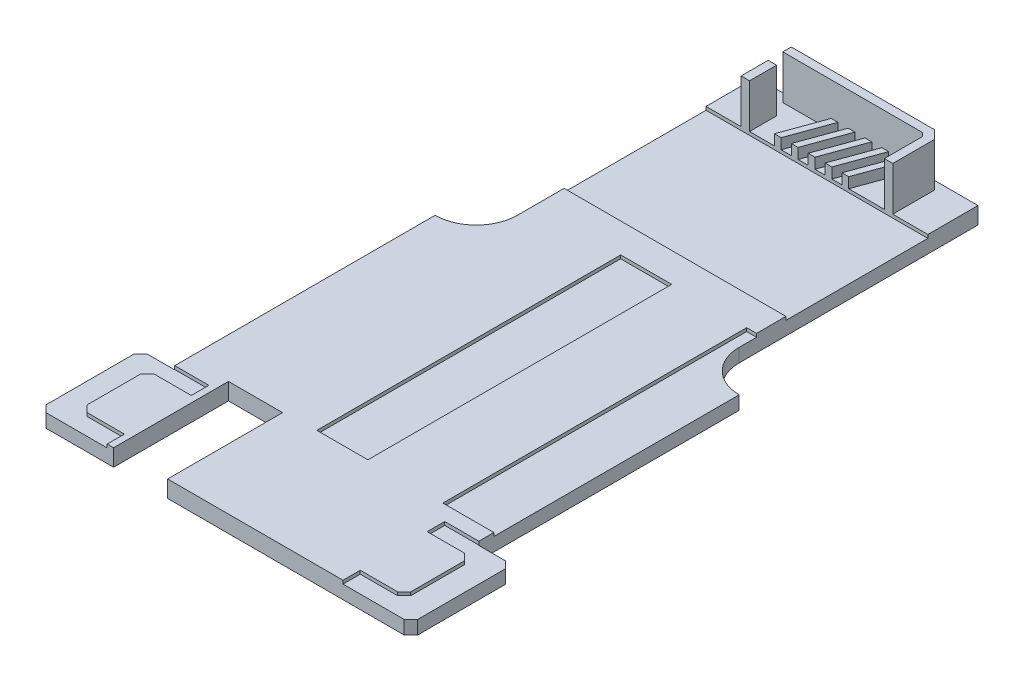
SolidWorks part; units mm, degrees
ref_plane "Front Plane" through (0, 0, 0) normal (0, 0, 1) x (1, 0, 0)
ref_plane "Top Plane" through (0, 0, 0) normal (0, 1, 0) x (1, 0, 0)
ref_plane "Right Plane" through (0, 0, 0) normal (1, 0, 0) x (0, 0, -1)
sketch "Sketch1" plane through (0, 0, 0) normal (0, 1, 0) x (1, 0, 0)
  line L1 (-45, 95) -> (45, 95)
  line L2 (-45, 95) -> (-45, -95)
  line L3 (-45, -95) -> (45, -95)
  line L4 (45, 95) -> (45, -95)
  line L5 (-45, 95) -> (45, -95) construction
  line L6 (-45, -95) -> (45, 95) construction
  point P0 (0, 0)
  dimension "D1" = 190
  dimension "D2" = 90
extrude "Boss-Extrude1" add sketch "Sketch1" along normal blind 5 contours L2 L1 L4 L3
sketch "Sketch2" plane through (0, 0, 0) normal (0, 1, 0) x (1, 0, 0)
  line L0 (-45, 95) -> (-45, -95) construction
  line L1 (-45, -65) -> (-55, -65)
  line L2 (-45, -65) -> (-45, -95)
  line L3 (-45, -95) -> (-55, -95)
  line L4 (-55, -65) -> (-55, -95)
  line L5 (45, 95) -> (45, -95) construction
  line L6 (45, -65) -> (55, -65)
  line L7 (45, -65) -> (45, -95)
  line L8 (45, -95) -> (55, -95)
  line L9 (55, -65) -> (55, -95)
  line L10 (-45, -95) -> (45, -95) construction
  dimension "D1" = 30
  dimension "D2" = 10
extrude "Boss-Extrude2" add sketch "Sketch2" along normal blind 5
chamfer "Chamfer1" distance 2 angle 45 4 edges at (55, 2.5, 95) (55, 2.5, 65) (-55, 2.5, 95) (-55, 2.5, 65)
sketch "Sketch3" plane through (0, 5, 0) normal (0, 1, 0) x (1, 0, 0)
  line L0 (-53, -95) -> (53, -95) construction
  line L1 (-33, -95) -> (-17, -95)
  line L2 (-33, -95) -> (-33, -61)
  line L3 (-33, -61) -> (-17, -61)
  line L4 (-17, -95) -> (-17, -61)
  line L5 (-55, -67) -> (-55, -93) construction
  dimension "D1" = 22
  dimension "D2" = 16
  dimension "D3" = 34
extrude "Cut-Extrude1" cut sketch "Sketch3" against normal blind 50 contours L2 L1 L4 L3
sketch "Sketch4" plane through (0, 5, 0) normal (0, 1, 0) x (1, 0, 0)
  line L0 (-45, 80.1598) -> (-45, 38.1598)
  line L1 (-45, 95) -> (-45, -65) construction
  line L2 (-48, 80.1598) -> (48, 80.1598) construction
  line L4 (-45, 38.1598) -> (45, 38.1598)
  line L5 (45, 95) -> (45, -65) construction
  line L6 (45, 38.1598) -> (45, 80.1598)
  line L7 (45, 80.1598) -> (-45, 80.1598)
  dimension "D1" = 42
extrude "Cut-Extrude2" cut sketch "Sketch4" against normal blind 1
sketch "Sketch7" plane through (0, 5, 0) normal (0, 1, 0) x (1, 0, 0)
  line L0 (-7.3823, 29.4629) -> (-7.3823, -60.4534)
  line L1 (-7.3823, -60.4534) -> (7.7177, -60.4534)
  line L2 (7.7177, -60.4534) -> (7.7177, 29.4629)
  line L3 (7.7177, 29.4629) -> (-7.3823, 29.4629)
  line L4 (29.9, 29.4629) -> (29.9, -60.4534)
  line L5 (29.9, -60.4534) -> (45, -60.4534)
  line L6 (45, 38.1598) -> (45, -65) construction
  line L7 (45, -60.4534) -> (45, 29.4629)
  line L8 (45, 29.4629) -> (29.9, 29.4629)
  line M17 (45, -65) -> (45, 38.1598)
  dimension "D1" = 15.1
  dimension "D2" = 15.1
extrude "Cut-Extrude7" cut sketch "Sketch7" against normal blind 1 contours L8 L4 L5 M17 | L3 L0 L1 L2 region at (37.45, 5, 15.4953)
sketch "Sketch8" plane through (0, 5, 0) normal (0, 1, 0) x (1, 0, 0)
  line L1 (-35, -65) -> (-35, -70) construction
  line L2 (-35, -70) -> (-46, -70) construction
  line L3 (-46, -70) -> (-48, -72) construction
  line L4 (-48, -72) -> (-48, -88) construction
  line L5 (-48, -88) -> (-46, -90) construction
  line L6 (-46, -90) -> (-35, -90) construction
  line L7 (-35, -90) -> (-35, -95) construction
  line L8 (-53, -95) -> (-33, -95) construction
  line L9 (-35, -95) -> (-35, -90) construction
  line L10 (-35, -95) -> (-53, -95) construction
  line L11 (-53, -95) -> (-55, -93) construction
  line L12 (-55, -93) -> (-55, -67) construction
  line L13 (-55, -67) -> (-53, -65) construction
  line L14 (-53, -65) -> (-35, -65) construction
  line L15 (-34.9, -70.1) -> (-45.9586, -70.1)
  line L16 (-45.9586, -70.1) -> (-47.9, -72.0414)
  line L17 (-47.9, -72.0414) -> (-47.9, -87.9586)
  line L18 (-47.9, -87.9586) -> (-45.9586, -89.9)
  line L19 (-45.9586, -89.9) -> (-34.9, -89.9)
  line L20 (-34.9, -89.9) -> (-34.9, -95.1)
  line L21 (-34.9, -95.1) -> (-53.0414, -95.1)
  line L22 (-53.0414, -95.1) -> (-55.1, -93.0414)
  line L23 (-55.1, -93.0414) -> (-55.1, -66.9586)
  line L24 (-55.1, -66.9586) -> (-53.0414, -64.9)
  line L25 (-53.0414, -64.9) -> (-34.9, -64.9)
  line L26 (-34.9, -64.9) -> (-34.9, -70.1)
  dimension "D1" = 0.1
extrude "Cut-Extrude8" cut sketch "Sketch8" against normal blind 1
mirror "Mirror1" about plane through (0, 0, 0) normal (1, 0, 0) of "Cut-Extrude8"
sketch "Sketch14" plane through (0, 0, 0) normal (0, 1, 0) x (1, 0, 0)
  line L0 (-45, 47.2671) -> (-34.685, 30.799)
  line L1 (-45, 80.1598) -> (-45, 38.1598) construction
  line L2 (-45, 38.1598) -> (-45, -64.9) construction
  line L3 (-45, 47.2671) -> (-45, 12.1668)
  line L4 (0, -6.2305) -> (0, 15.6399) construction
  line L5 (45, 47.2671) -> (45, 12.1668)
  line L6 (45, 47.2671) -> (34.685, 30.799)
  arc A0 (-34.685, 30.799) -> (-45, 12.1668) centre (-45, 24.3381) cw
  arc A1 (34.685, 30.799) -> (45, 12.1668) centre (45, 24.3381) ccw
extrude "Cut-Extrude9" cut sketch "Sketch14" along normal through all both and the other way through all
sketch "Sketch15" plane through (0, 0, 0) normal (0, 1, 0) x (1, 0, 0)
  line L0 (-34.685, 30.799) -> (-39.2956, 38.1598) construction
  line L2 (-34.685, 30.799) -> (-39.2956, 38.1598)
  line L5 (-32.9901, 31.8607) -> (-36.9356, 38.1598)
  line L9 (-45, 12.1668) -> (-45, 10.1668)
  line L10 (0, 0) -> (0, 12.1668)
  line L11 (45, 12.1668) -> (45, 10.1668)
  line L12 (34.685, 30.799) -> (39.2956, 38.1598)
  line L17 (32.9901, 31.8607) -> (36.9356, 38.1598)
  line L18 (-39.2956, 38.1598) -> (-36.9356, 38.1598)
  line L19 (-39.2956, 38.1598) -> (39.2956, 38.1598) construction
  line L20 (-32.9901, 31.8607) -> (-37.6006, 39.2215) construction
  line L21 (-45, 47.2671) -> (-39.2956, 38.1598) construction
  line L22 (-43.305, 48.3288) -> (-37.6006, 39.2215) construction
  line L23 (39.2956, 38.1598) -> (36.9356, 38.1598)
  arc A0 (-45, 12.1668) -> (-34.685, 30.799) centre (-45, 24.3381) ccw construction
  arc A1 (-45, 12.1668) -> (-34.685, 30.799) centre (-45, 24.3381) ccw
  arc A2 (-45, 10.1668) -> (-32.9901, 31.8607) centre (-45, 24.3381) ccw
  arc A3 (45, 12.1668) -> (34.685, 30.799) centre (45, 24.3381) cw
  arc A4 (45, 10.1668) -> (32.9901, 31.8607) centre (45, 24.3381) cw
  dimension "D1" = 2
extrude "Boss-Extrude3" [suppressed] add sketch "Sketch15" along normal blind 2 from surface contours A1 L2 L18 L5 A2 L9 | A3 L12 L23 L17 A4 L11
sketch "Sketch16" plane through (0, 0, 0) normal (0, 1, 0) x (1, 0, 0)
  line L0 (-32.8287, 95) -> (-32.8287, 24.3381)
  line L1 (-45, 95) -> (45, 95) construction
  line L4 (-34.685, 30.799) -> (-45, 47.2671)
  line L5 (-45, 47.2671) -> (-45, 95)
  line L6 (-45, 95) -> (-32.8287, 95)
  line L7 (0, 0) -> (0, 50000) construction
  line L13 (45, 95) -> (32.8287, 95)
  line L14 (45, 47.2671) -> (45, 95)
  line L15 (34.685, 30.799) -> (45, 47.2671)
  line L16 (32.8287, 95) -> (32.8287, 24.3381)
  arc A0 (-45, 12.1668) -> (-34.685, 30.799) centre (-45, 24.3381) ccw construction
  arc A1 (-32.8287, 24.3381) -> (-34.685, 30.799) centre (-45, 24.3381) ccw
  arc A2 (32.8287, 24.3381) -> (34.685, 30.799) centre (45, 24.3381) cw
extrude "Cut-Extrude10" cut sketch "Sketch16" along normal through all both and the other way through all
sketch "Sketch17" plane through (0, 0, 0) normal (0, 1, 0) x (1, 0, 0)
  line L0 (-19.94, 80.1598) -> (-19.94, 88.1598)
  line L1 (32.8287, 80.1598) -> (-32.8287, 80.1598) construction
  line L2 (-19.94, 69.0848) -> (-19.94, 88.4854) construction
  line L4 (-22.44, 92.4998) -> (18.94, 92.4998)
  line L5 (18.94, 92.4998) -> (19.94, 91.4998)
  line L7 (19.94, 91.4998) -> (18.94, 92.4998) construction
  line L10 (19.94, 91.4998) -> (19.94, 80.1598)
  line L11 (19.94, 69.0848) -> (19.94, 88.4854) construction
  line L12 (-22.44, 80.1598) -> (-22.44, 88.1598)
  line L14 (-22.44, 94.9998) -> (19.9756, 94.9998)
  line L15 (19.9756, 94.9998) -> (22.44, 92.5354)
  line L16 (22.44, 92.5354) -> (22.44, 80.1598)
  line L17 (-22.44, 80.1598) -> (-19.94, 80.1598)
  line L18 (19.94, 80.1598) -> (22.44, 80.1598)
  line L19 (-22.44, 88.1598) -> (-19.94, 88.1598)
  line L20 (-22.44, 92.4998) -> (-22.44, 94.9998)
  line L21 (-22.44, 80.1598) -> (-22.44, 92.5354) construction
  line L22 (-19.94, 80.1598) -> (-19.94, 91.4998) construction
  line L23 (-19.94, 91.4998) -> (-18.94, 92.4998) construction
  line L24 (-18.94, 92.4998) -> (18.94, 92.4998) construction
  line L25 (-19.9756, 94.9998) -> (19.9756, 94.9998) construction
  line L26 (-22.44, 92.5354) -> (-19.9756, 94.9998) construction
  dimension "D2" = 8
  dimension "D1" = 2.5
extrude "Boss-Extrude4" add sketch "Sketch17" along normal blind 13 from surface starting at face at (0, 5, -87.5799)
sketch "Sketch18" plane through (0, 5, 0) normal (0, 1, 0) x (1, 0, 0)
  line L6 (-12.5996, 80.1598) -> (-10.5996, 80.1598)
  line L7 (19.94, 80.1598) -> (-19.94, 80.1598) construction
  line L8 (-10.5996, 80.1598) -> (-6.1082, 92.4998)
  line L9 (-22.44, 92.4998) -> (18.94, 92.4998) construction
  line L10 (-6.1082, 92.4998) -> (-8.1082, 92.4998)
  line L11 (-8.1082, 92.4998) -> (-12.5996, 80.1598)
  line L12 (-3.1082, 92.4998) -> (-7.5996, 80.1598)
  line L13 (-7.5996, 80.1598) -> (-5.5996, 80.1598)
  line L14 (-5.5996, 80.1598) -> (-1.1082, 92.4998)
  line L15 (-1.1082, 92.4998) -> (-3.1082, 92.4998)
  line L16 (1.8918, 92.4998) -> (-2.5996, 80.1598)
  line L17 (-2.5996, 80.1598) -> (-0.5996, 80.1598)
  line L18 (-0.5996, 80.1598) -> (3.8918, 92.4998)
  line L19 (3.8918, 92.4998) -> (1.8918, 92.4998)
  line L20 (6.8918, 92.4998) -> (2.4004, 80.1598)
  line L21 (2.4004, 80.1598) -> (4.4004, 80.1598)
  line L22 (4.4004, 80.1598) -> (8.8918, 92.4998)
  line L23 (8.8918, 92.4998) -> (6.8918, 92.4998)
  line L24 (11.8918, 92.4998) -> (7.4004, 80.1598)
  line L25 (7.4004, 80.1598) -> (9.4004, 80.1598)
  line L26 (9.4004, 80.1598) -> (13.8918, 92.4998)
  line L27 (13.8918, 92.4998) -> (11.8918, 92.4998)
  dimension "D1" = 2
  dimension "D2" = 70
  dimension "D3" = 5
extrude "Boss-Extrude5" add sketch "Sketch18" along normal blind 3.1
